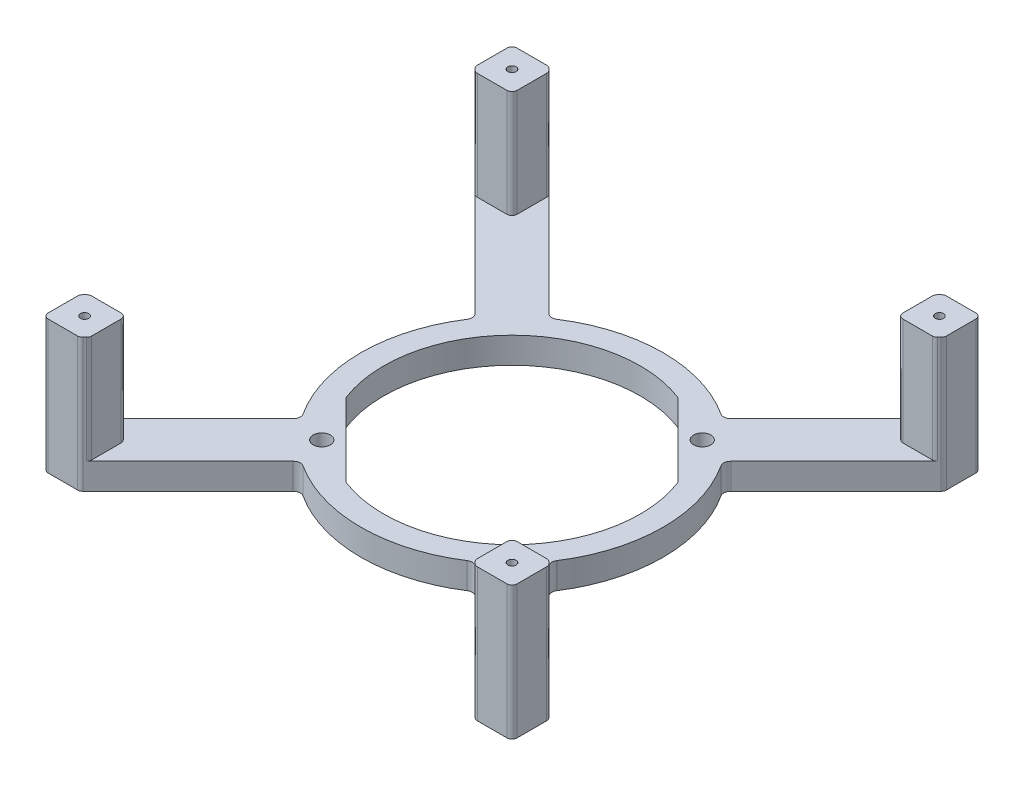
SolidWorks part; units mm, degrees
ref_plane "Front Plane" through (0, 0, 0) normal (0, 0, 1) x (1, 0, 0)
ref_plane "Top Plane" through (0, 0, 0) normal (0, 1, 0) x (1, 0, 0)
ref_plane "Right Plane" through (0, 0, 0) normal (1, 0, 0) x (0, 0, -1)
sketch "Sketch1" plane through (0, 0, 0) normal (0, 1, 0) x (1, 0, 0)
  line L0 (0, 50) -> (100, 50) construction
  line L1 (0, 0) -> (100, 0) construction
  line L2 (0, 0) -> (0, 100) construction
  line L3 (0, 100) -> (100, 100) construction
  line L4 (100, 0) -> (100, 100) construction
  line L5 (50, 0) -> (50, 50) construction
  line L6 (50, 50) -> (50, 100) construction
  line L7 (6, 95) -> (11.6569, 95)
  line L8 (5, 95) -> (95, 95) construction
  line L9 (50, 50) -> (110.8194, 110.8194) construction
  line L10 (50, 50) -> (-8.0727, 108.0727) construction
  line L11 (72.981, 58.8388) -> (58.8388, 72.981)
  line L12 (41.1612, 27.019) -> (27.019, 41.1612)
  line L13 (5, 95) -> (5, 5) construction
  line L14 (5, 5) -> (95, 5) construction
  line L15 (95, 95) -> (95, 5) construction
  line L16 (12.364, 94.7071) -> (32.5387, 74.5324)
  line L17 (5, 94) -> (5, 88.3431)
  line L18 (5.2929, 87.636) -> (25.4676, 67.4613)
  line L19 (50, 50) -> (0, 0) construction
  line L20 (95, 94) -> (95, 88.3431)
  line L21 (94.7071, 87.636) -> (74.5324, 67.4613)
  line L22 (94, 95) -> (88.3431, 95)
  line L23 (87.636, 94.7071) -> (67.4613, 74.5324)
  line L24 (50, 50) -> (108.0727, 108.0727) construction
  line L25 (94, 5) -> (88.3431, 5)
  line L26 (87.636, 5.2929) -> (67.4613, 25.4676)
  line L27 (95, 6) -> (95, 11.6569)
  line L28 (94.7071, 12.364) -> (74.5324, 32.5387)
  line L29 (50, 50) -> (108.0727, -8.0727) construction
  line L30 (5, 6) -> (5, 11.6569)
  line L31 (5.2929, 12.364) -> (25.4676, 32.5387)
  line L32 (6, 5) -> (11.6569, 5)
  line L33 (12.364, 5.2929) -> (32.5387, 25.4676)
  line L34 (50, 50) -> (-8.0727, -8.0727) construction
  arc A0 (58.8388, 72.981) -> (27.019, 41.1612) centre (50, 50) ccw
  arc A1 (41.1612, 27.019) -> (72.981, 58.8388) centre (50, 50) ccw
  arc A2 (25.6492, 65.7492) -> (25.6492, 34.2508) centre (50, 50) ccw
  arc A3 (11.6569, 95) -> (12.364, 94.7071) centre (11.6569, 94) cw
  arc A4 (6, 95) -> (5, 94) centre (6, 94) ccw
  arc A5 (5, 88.3431) -> (5.2929, 87.636) centre (6, 88.3431) ccw
  arc A6 (95, 88.3431) -> (94.7071, 87.636) centre (94, 88.3431) cw
  arc A7 (95, 94) -> (94, 95) centre (94, 94) ccw
  arc A8 (88.3431, 95) -> (87.636, 94.7071) centre (88.3431, 94) ccw
  arc A9 (88.3431, 5) -> (87.636, 5.2929) centre (88.3431, 6) cw
  arc A10 (94, 5) -> (95, 6) centre (94, 6) ccw
  arc A11 (95, 11.6569) -> (94.7071, 12.364) centre (94, 11.6569) ccw
  arc A12 (5, 11.6569) -> (5.2929, 12.364) centre (6, 11.6569) cw
  arc A13 (5, 6) -> (6, 5) centre (6, 6) ccw
  arc A14 (11.6569, 5) -> (12.364, 5.2929) centre (11.6569, 6) ccw
  arc A15 (65.7492, 74.3508) -> (34.2508, 74.3508) centre (50, 50) ccw
  arc A16 (74.3508, 34.2508) -> (74.3508, 65.7492) centre (50, 50) ccw
  arc A17 (34.2508, 25.6492) -> (65.7492, 25.6492) centre (50, 50) ccw
  arc A18 (74.5324, 32.5387) -> (74.3508, 34.2508) centre (75.5007, 33.5071) cw
  arc A19 (67.4613, 25.4676) -> (65.7492, 25.6492) centre (66.4929, 24.4993) ccw
  arc A20 (32.5387, 25.4676) -> (34.2508, 25.6492) centre (33.5071, 24.4993) cw
  arc A21 (25.4676, 32.5387) -> (25.6492, 34.2508) centre (24.4993, 33.5071) ccw
  arc A22 (25.4676, 67.4613) -> (25.6492, 65.7492) centre (24.4993, 66.4929) cw
  arc A23 (32.5387, 74.5324) -> (34.2508, 74.3508) centre (33.5071, 75.5007) ccw
  arc A24 (74.5324, 67.4613) -> (74.3508, 65.7492) centre (75.5007, 66.4929) ccw
  arc A25 (67.4613, 74.5324) -> (65.7492, 74.3508) centre (66.4929, 75.5007) cw
  point P27 (12.0711, 95)
  point P33 (5, 87.9289)
  point P72 (50, 50)
  point P86 (31.7496, 31.7496)
  point P87 (68.2504, 68.2504)
  dimension "D3" = 58
  dimension "D5" = 45
  dimension "D12" = 1
  dimension "D16" = 1.3694
  dimension "D1" = 100
  dimension "D2" = 100
  dimension "D4" = 5
  dimension "D6" = 45
  dimension "D7" = 5
  dimension "D8" = 20
  dimension "D9" = 10
  dimension "D10" = 22.5
  dimension "D11" = 5
  dimension "D13" = 10
  dimension "D14" = 5
  dimension "D17" = 25.81
  dimension "D15" = 4
extrude "Boss-Extrude1" add sketch "Sketch1" along normal blind 5
sketch "Sketch4" plane through (0, 5, 0) normal (0, 1, 0) x (1, 0, 0)
  line L0 (5.2929, 94.7071) -> (94.7071, 5.2929) construction
  line L1 (5.2929, 5.2929) -> (94.7071, 94.7071) construction
  arc A0 (94, 5) -> (95, 6) centre (94, 6) ccw construction
  arc A1 (6, 95) -> (5, 94) centre (6, 94) ccw construction
  arc A3 (5, 6) -> (6, 5) centre (6, 6) ccw construction
  arc A4 (95, 94) -> (94, 95) centre (94, 94) ccw construction
  point P3 (50, 50)
  point P17 (31.7496, 31.7496)
  point P18 (68.2504, 68.2504)
  dimension "D1" = 25.81
  dimension "D2" = 0
hole_wizard "Tap Drill for M4x0.7 Tap1" positions "3DSketch2" profile "Sketch5" hole size "M4x0.7" standard "ANSI Metric" end condition through all
sketch3d "3DSketch2"
  point P0 (31.7496, 5, -31.7496)
  point P3 (68.2504, 5, -68.2504)
sketch "Sketch5" plane through (31.7496, 5, -31.7496) normal (1, 0, 0) x (0, 0, 1)
  line L0 (0, 0) -> (0, 5)
  line L1 (0, 5) -> (1.65, 5)
  line L2 (1.65, 5) -> (1.65, 0)
  line L5 (1.65, 0) -> (0, 0)
  line L11 (0, -6.35) -> (0, 107.95) construction
  dimension "Thru Hole Dia." = 3.3
  dimension "Thru Hole Depth" = 5
sketch "Sketch6" plane through (0, 5, 0) normal (0, 1, 0) x (1, 0, 0)
  line L1 (6, 95) -> (11.6569, 95)
  line L2 (5, 94) -> (5, 88.3431)
  line L5 (11.6569, 95) -> (6, 95) construction
  line L6 (5, 94) -> (5, 88.3431) construction
  line L7 (13, 93.6569) -> (13, 88)
  line L8 (12, 87) -> (6.3431, 87)
  line L9 (5.636, 87.2929) -> (5.2929, 87.636)
  line L10 (5.2929, 87.636) -> (25.4676, 67.4613) construction
  line L11 (12.7071, 94.364) -> (12.364, 94.7071)
  line L12 (32.5387, 74.5324) -> (12.364, 94.7071) construction
  arc A0 (5.2929, 87.636) -> (5, 88.3431) centre (6, 88.3431) cw
  arc A1 (5.636, 87.2929) -> (6.3431, 87) centre (6.3431, 88) ccw
  arc A2 (13, 88) -> (12, 87) centre (12, 88) cw
  arc A3 (12.7071, 94.364) -> (13, 93.6569) centre (12, 93.6569) cw
  arc A4 (12.364, 94.7071) -> (11.6569, 95) centre (11.6569, 94) ccw
  arc A5 (6, 95) -> (5, 94) centre (6, 94) ccw
  point P18 (5.9289, 87)
  point P23 (13, 94.0711)
  dimension "D5" = 1
  dimension "D1" = 0
  dimension "D2" = 0
  dimension "D3" = 8
  dimension "D4" = 8
extrude "Boss-Extrude2" add sketch "Sketch6" along normal blind 20.6
sketch "Sketch7" plane through (0, 25.6, 0) normal (0, 1, 0) x (1, 0, 0)
  line L0 (5.2929, 94.7071) -> (94.7071, 5.2929) construction
  line L1 (5, 94) -> (5, 88.3431) construction
  point P0 (9, 91)
  dimension "D1" = 4
hole_wizard "Tap Drill for M2x0.4 Tap1" positions "3DSketch3" profile "Sketch9" hole size "M2x0.4" standard "ANSI Metric"
sketch3d "3DSketch3"
  point P0 (9, 25.6, -91)
sketch "Sketch9" plane through (9, 25.6, -91) normal (1, 0, 0) x (0, 0, 1)
  line L0 (0, 0) -> (0, 4.4807)
  line L1 (0, 4.4807) -> (0.8, 4)
  line L2 (0.8, 4) -> (0.8, 0)
  line L5 (0.8, 0) -> (0, 0)
  line L10 (0, 4.4807) -> (-0.8, 4) construction
  line L11 (0, -6.35) -> (0, 107.95) construction
  dimension "Hole Dia." = 1.6
  dimension "Hole Depth" = 4
  dimension "Drill Angle" = 118
ref_axis "Axis1" through (50, 5, -50) along (0, -1, 0)
pattern_circular "CirPattern1" count 4 every 90 about axis through (50, 5, -50) along (0, -1, 0) of "Boss-Extrude2", "Tap Drill for M2x0.4 Tap1"
